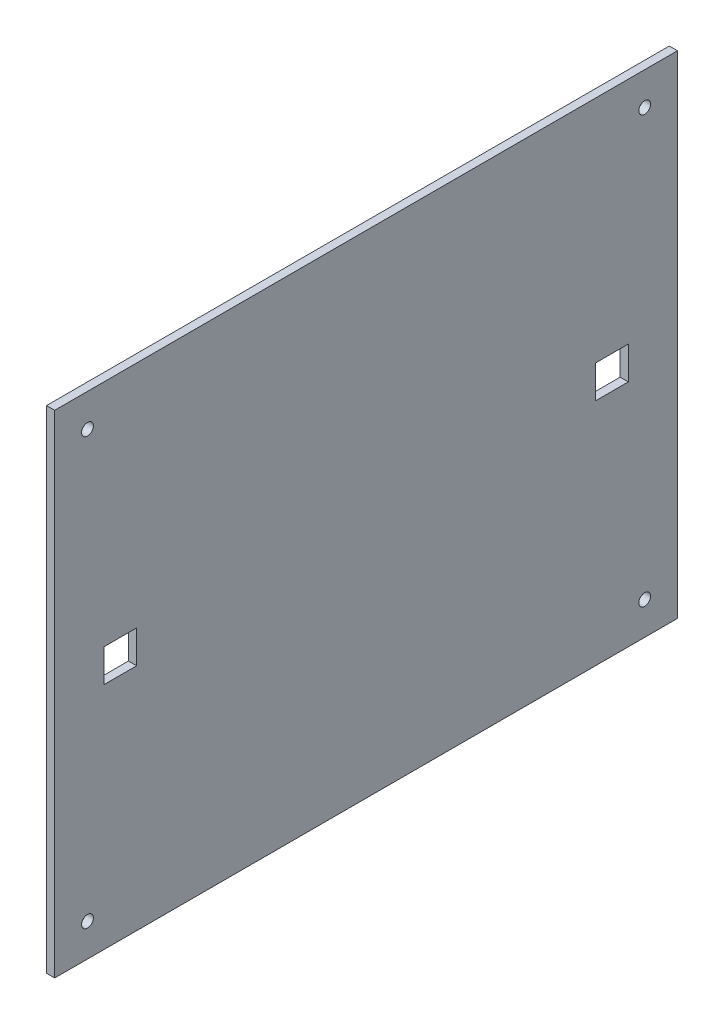
SolidWorks part; units mm, degrees
ref_plane "Front Plane" through (0, 0, 0) normal (0, 0, 1) x (1, 0, 0)
ref_plane "Top Plane" through (0, 0, 0) normal (0, 1, 0) x (1, 0, 0)
ref_plane "Right Plane" through (0, 0, 0) normal (1, 0, 0) x (0, 0, -1)
sketch "Sketch1" plane through (0, 0, 0) normal (1, 0, 0) x (0, 0, -1)
  line L1 (0, 0) -> (241.3, 0)
  line L2 (0, 0) -> (0, 190.5)
  line L3 (0, 190.5) -> (241.3, 190.5)
  line L4 (241.3, 0) -> (241.3, 190.5)
  dimension "D1" = 241.3
  dimension "D2" = 190.5
extrude "Boss-Extrude1" add sketch "Sketch1" along normal blind 3.175
sketch "Sketch2" plane through (3.175, 0, 0) normal (1, 0, 0) x (0, 0, -1)
  line L2 (-1000, 95.25) -> (49000, 95.25) construction
  line L3 (0, 190.5) -> (0, 0) construction
  line L4 (120.65, -809.5) -> (120.65, 49190.5) construction
  line L5 (241.3, 190.5) -> (0, 190.5) construction
  line L6 (1228.6, 95.25) -> (-48771.4, 95.25) construction
  line L7 (241.3, 0) -> (241.3, 190.5) construction
  line L8 (0, 0) -> (241.3, 0) construction
  circle A8 centre (228.6, 12.7) radius 2.286
  circle A9 centre (228.6, 177.8) radius 2.286
  circle A10 centre (12.7, 12.7) radius 2.286
  circle A11 centre (12.7, 177.8) radius 2.286
  point P15 (0, 95.25)
  point P20 (120.65, 190.5)
  dimension "D1" = 4.572
  dimension "D2" = 12.7
  dimension "D3" = 12.7
extrude "Cut-Extrude1" cut sketch "Sketch2" against normal through all
sketch "Sketch3" plane through (3.175, 0, 0) normal (1, 0, 0) x (0, 0, -1)
  line L0 (0, 190.5) -> (0, 0) construction
  line L1 (19.05, 101.6) -> (31.75, 101.6)
  line L2 (19.05, 101.6) -> (19.05, 88.9)
  line L3 (19.05, 88.9) -> (31.75, 88.9)
  line L4 (31.75, 101.6) -> (31.75, 88.9)
  line L5 (209.55, 101.6) -> (222.25, 101.6)
  line L6 (209.55, 101.6) -> (209.55, 88.9)
  line L7 (209.55, 88.9) -> (222.25, 88.9)
  line L8 (222.25, 101.6) -> (222.25, 88.9)
  line L9 (241.3, 0) -> (241.3, 190.5) construction
  point P8 (19.05, 95.25)
  point P9 (209.55, 95.25)
  point P12 (0, 95.25)
  dimension "D1" = 12.7
  dimension "D2" = 12.7
  dimension "D3" = 19.05
  dimension "D4" = 19.05
extrude "Cut-Extrude2" cut sketch "Sketch3" against normal through all
